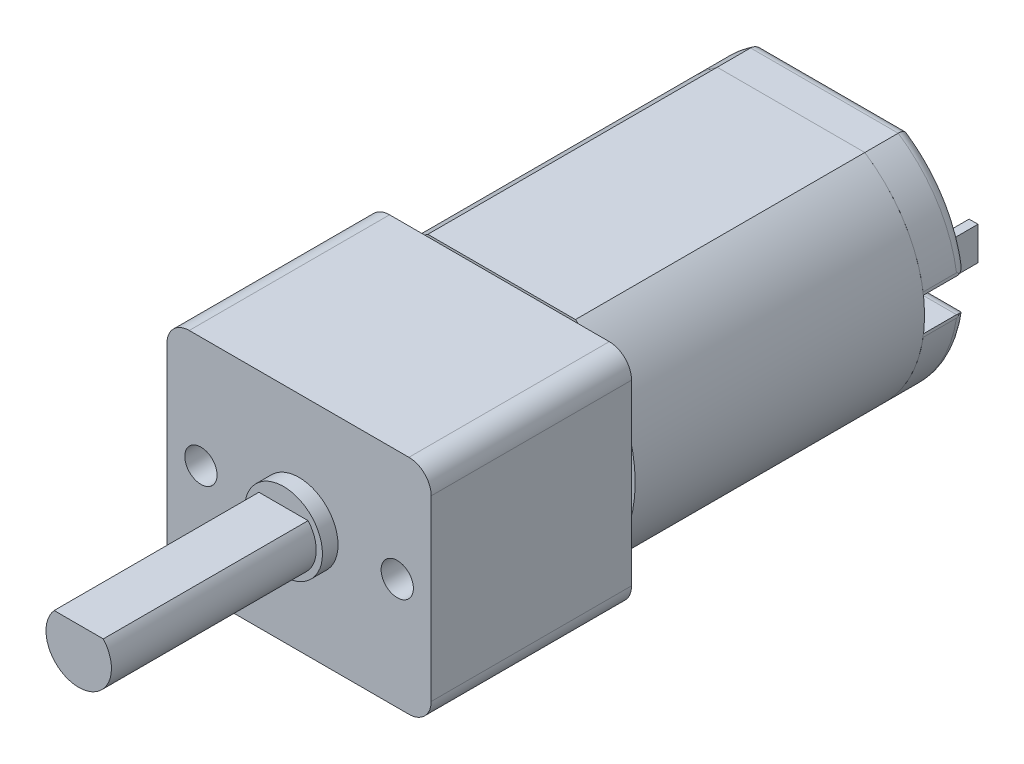
SolidWorks part; units mm, degrees
ref_plane "Front Plane" through (0, 0, 0) normal (0, 0, 1) x (1, 0, 0)
ref_plane "Top Plane" through (0, 0, 0) normal (0, 1, 0) x (1, 0, 0)
ref_plane "Right Plane" through (0, 0, 0) normal (1, 0, 0) x (0, 0, -1)
sketch "Sketch1" plane through (0, 0, 0) normal (0, 0, 1) x (1, 0, 0)
  line L1 (-4.935, 5) -> (4.935, 5)
  line L2 (-5.935, 4) -> (-5.935, -4)
  line L3 (-4.935, -5) -> (4.935, -5)
  line L4 (5.935, 4) -> (5.935, -4)
  line L5 (-5.935, 5) -> (5.935, -5) construction
  line L6 (-5.935, -5) -> (5.935, 5) construction
  arc A0 (4.935, 5) -> (5.935, 4) centre (4.935, 4) cw
  arc A1 (-4.935, 5) -> (-5.935, 4) centre (-4.935, 4) ccw
  arc A2 (4.935, -5) -> (5.935, -4) centre (4.935, -4) ccw
  arc A3 (-5.935, -4) -> (-4.935, -5) centre (-4.935, -4) ccw
  circle A4 centre (0, 0) radius 1.75
  circle A5 centre (-4.41, 0) radius 0.725
  circle A6 centre (4.41, 0) radius 0.725
  point P0 (0, 0)
  dimension "D3" = 1
  dimension "D4" = 0.8
  dimension "D5" = 3.5
  dimension "D6" = 0.8
  dimension "D7" = 1.45
  dimension "D1" = 10
  dimension "D2" = 11.87
extrude "Boss-Extrude1" add sketch "Sketch1" along normal blind 9 contours L3 A2 L4 A0 L1 A1 L2 A3 | A5 | A6
extrude "Boss-Extrude2" add sketch "Sketch1<3>" along normal blind 0.7 from surface contours A4 starting at face at (-3.685, 0, 9)
sketch "Sketch1<3>" plane through (0, 0, 0) normal (0, 0, 1) x (1, 0, 0) same geometry as "Sketch1"
sketch "Sketch2" plane through (0, 0, 0) normal (0, 0, -1) x (-1, 0, 0)
  line L0 (-3.3166, 5) -> (3.3166, 5)
  line L1 (4.935, 5) -> (-4.935, 5) construction
  line L2 (-3.3166, -5) -> (3.3166, -5)
  line L3 (4.935, -5) -> (-4.935, -5) construction
  line L4 (0, 0) -> (0, 6.6634) construction
  line L5 (-5.9529, 0.75) -> (-4, 0.75)
  line L7 (-5.9529, -0.75) -> (-4, -0.75)
  line L8 (-4, 0.75) -> (-4, -0.75)
  line L9 (5.9529, -0.75) -> (4, -0.75)
  line L10 (4, 0.75) -> (4, -0.75)
  line L11 (5.9529, 0.75) -> (4, 0.75)
  line L13 (-4.4, 0.75) -> (-4.4, -0.75)
  line L14 (4.4, 0.75) -> (4.4, -0.75)
  arc A0 (-3.3166, 5) -> (-3.3166, -5) centre (0, 0) ccw
  arc A1 (3.3166, -5) -> (3.3166, 5) centre (0, 0) ccw
  circle A2 centre (0, 0) radius 2.5
  point P15 (-4, 0)
  line M18 (5.935, -4) -> (5.935, 4)
  line M20 (4.935, 5) -> (-4.935, 5)
  line M22 (-5.935, 4) -> (-5.935, -4)
  line M24 (-4.935, -5) -> (4.935, -5)
  circle M25 centre (4.41, 0) radius 0.725
  circle M26 centre (-4.41, 0) radius 0.725
  dimension "D1" = 12
  dimension "D2" = 5
  dimension "D5" = 4
  dimension "D3" = 0.4
  dimension "D4" = 0.4
extrude "Boss-Extrude4" add sketch "Sketch2" along normal blind 13 from offset 0.1 separate body contours A0 L2 A1 L0
extrude "Boss-Extrude5" add sketch "Sketch2<4>" along normal blind 2 from surface separate body contours L4 A2 L0 A0 L5 L8 L7 M24 M22 M26 | L4 L2 A1 L9 L10 L11 A2 M18 M25 M20 | L8 M26 | L10 M25 | A2 L4 | L4 A2 region at (-1.7178, 1.7178, 0) region at (1.6583, 4.8448, 0) region at (3.8713, 0, 0) region at (-3.8713, 0, 0) starting at face at (0, 0, -13.1)
sketch "Sketch2<4>" plane through (0, 0, 0) normal (0, 0, -1) x (-1, 0, 0) same geometry as "Sketch2"
extrude "Boss-Extrude6" add sketch "Sketch2<5>" along normal blind 1 from surface contours A2 starting at face at (0, 0, -15.1)
sketch "Sketch2<5>" plane through (0, 0, 0) normal (0, 0, -1) x (-1, 0, 0) same geometry as "Sketch2"
extrude "Boss-Extrude7" add sketch "Sketch2<7>" along normal blind 4 from surface separate body contours L13 L8 M26 | L5 L13 L8 M26 | L13 L7 L8 M26 | L14 L11 L10 M25 | L14 L10 M25 | L14 L10 L9 M25 region at (4.1378, 0.7062, 0) region at (-4.1378, 0.7062, 0) region at (4.2061, 0, 0) region at (4.1378, -0.7062, 0) region at (-4.2061, 0, 0) region at (-4.1378, -0.7062, 0) starting at face at (0, 0, -13.1)
sketch "Sketch2<7>" plane through (0, 0, 0) normal (0, 0, -1) x (-1, 0, 0) same geometry as "Sketch2"
sketch "Sketch3" plane through (0, 0, 9.7) normal (0, 0, 1) x (1, 0, 0)
  line L0 (-1.1045, 0.97) -> (1.1045, 0.97)
  arc A0 (-1.1045, 0.97) -> (1.1045, 0.97) centre (0, 0) ccw
  dimension "D1" = 2.94
  dimension "D2" = 2.44
extrude "Boss-Extrude8" add sketch "Sketch3" along normal blind 9.2 separate body
sketch "Sketch4" plane through (0, 0, -16.1) normal (0, 0, -1) x (-1, 0, 0)
  circle A0 centre (0, 0) radius 1.1579
  dimension "D1" = 2.3158
extrude "Cut-Extrude2" cut sketch "Sketch4" against normal blind 0.5
fillet "Fillet1" radius 0.5 13 edges at (4.9675, -0.75, -15.1) (4, 0, -15.1) (4.9675, 0.75, -15.1) (5.0636, 3.2187, -15.1) (0, 5, -15.1) (-5.0636, 3.2187, -15.1) (-4.9675, 0.75, -15.1) (-4, 0, -15.1) (-4.9675, -0.75, -15.1) (-5.0636, -3.2187, -15.1) (0, -5, -15.1) (5.0636, -3.2187, -15.1) (-2.5, 0, -15.1)
ref_axis "Ось1" through (0, 0, 27.5844) along (0, 0, -1)
sketch "Эскиз1" plane through (0, 0, 18.9) normal (0, 0, 1) x (1, 0, 0)
  circle A0 centre (0, 0) radius 1.45
extrude "Бобышка-Вытянуть1" [suppressed] add sketch "Эскиз1" along normal blind 12.13
equation "\"D4@Sketch2\"=\"D3@Sketch2\""
